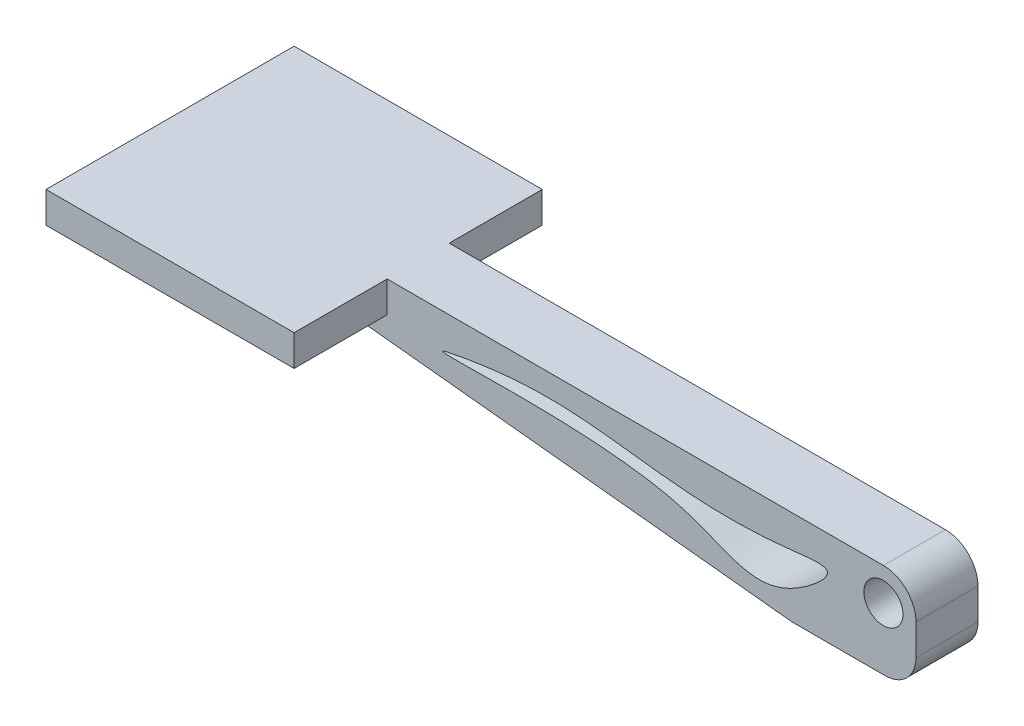
SolidWorks part; units mm, degrees
material "PET"
ref_plane "Front Plane" through (0, 0, 0) normal (0, 0, 1) x (1, 0, 0)
ref_plane "Top Plane" through (0, 0, 0) normal (0, 1, 0) x (1, 0, 0)
ref_plane "Right Plane" through (0, 0, 0) normal (1, 0, 0) x (0, 0, -1)
sketch "Sketch1" plane through (0, 0, 0) normal (0, 0, 1) x (1, 0, 0)
  line L1 (-201.0104, -2.2056) -> (-232.486, -2.2056)
  line L2 (-239.986, 5.2944) -> (-239.986, 10.5)
  line L3 (0, 10.5) -> (-199.9694, 10.5)
  line L4 (-199.9694, 10.5) -> (-199.9694, -2.2056)
  line L5 (-239.986, 10.5) -> (-199.9694, 10.5)
  line L6 (10.5, 0) -> (10.5, -10)
  line L7 (0.5, -20) -> (-29.5, -20)
  line L8 (-29.5, -20) -> (-198.934, -2.3137)
  circle A0 centre (0, 0) radius 6.3
  circle A1 centre (0, 0) radius 10.5
  arc A2 (-232.486, -2.2056) -> (-239.986, 5.2944) centre (-232.486, 5.2944) cw
  arc A3 (-201.0104, -2.2056) -> (-198.934, -2.3137) centre (-201.0104, -22.2056) cw
  arc A4 (0.5, -20) -> (10.5, -10) centre (0.5, -10) ccw
  spline S0 degree 3 poles (-11.8774, 2.3896) (-69.1666, -5.9397) (-91.2496, 8.2956) (-167.3142, -4.5164) (-66.6605, 5.706) (-39.3547, -20.8236) (-11.8774, 2.3896) (-69.1666, -5.9397) (-91.2496, 8.2956) knots -0.251012 -0.108125 -0.045537 0 0.381705 0.44528 0.748988 0.891875 0.954463 1 1.381705 1.44528 1.748988 only from (-29.5, 0) to (-29.5, 0)
  point P23 (10.5, -20)
  dimension "D1" = 12.6
  dimension "D2" = 21
  dimension "D8" = 7.5
  dimension "D9" = 20
  dimension "D10" = 10
  dimension "D3" = 199.9694
  dimension "D4" = 20
  dimension "D5" = 40.0166
  dimension "D6" = 40
  dimension "D7" = 170.3546
extrude "Boss-Extrude2" add sketch "Sketch1" along normal blind 10 and the other way blind 10 contours A1 A0 | A1 L3 L4 | L5 L2 L1 L4 region at (-216.7482, 0.3178, 0) region at (7.2146, 7.2146, 0)
sketch "Sketch2" plane through (0, 10.5, 0) normal (0, 1, 0) x (1, 0, 0)
  line L0 (0, 0) -> (-200, 0)
  line L1 (-201.0104, 0) -> (-232.486, 0) construction
  line L3 (-240, -40) -> (-160, -40)
  line L4 (-240, -40) -> (-240, 40)
  line L5 (-240, 40) -> (-160, 40)
  line L6 (-160, -40) -> (-160, 40)
  line L7 (-240, -40) -> (-160, 40) construction
  line L8 (-240, 40) -> (-160, -40) construction
  line M2 (-239.986, 10) -> (-239.986, -10)
  line M3 (-239.986, -10) -> (0, -10)
  line M5 (0, 10) -> (-239.986, 10)
  dimension "D1" = 200
  dimension "D2" = 80
  dimension "D3" = 80
extrude "Boss-Extrude5" add sketch "Sketch2" against normal blind 10 contours L3 L6 L5 L4 M3 M2 M5 | L6 M3 M5 M2 region at (-200, 10.5, -38.8686) region at (-199.993, 10.5, 9.1755)
